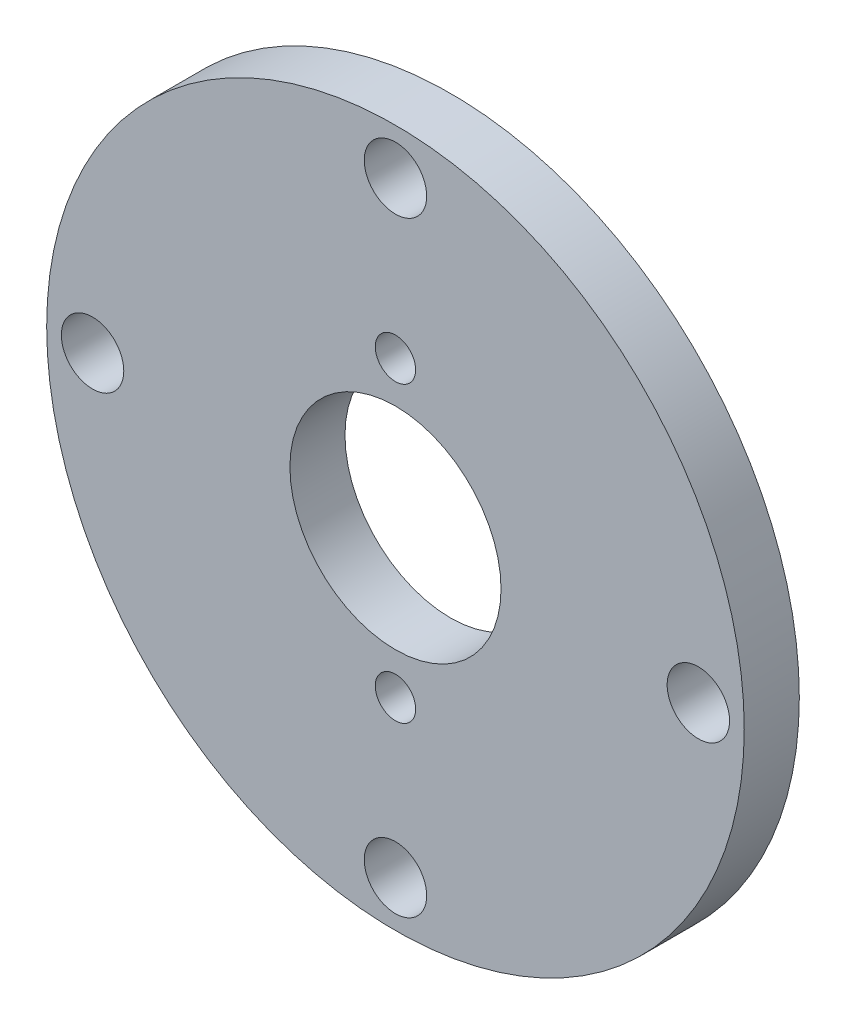
SolidWorks part; units mm, degrees
ref_plane "Front Plane" through (0, 0, 0) normal (0, 0, 1) x (1, 0, 0)
ref_plane "Top Plane" through (0, 0, 0) normal (0, 1, 0) x (1, 0, 0)
ref_plane "Right Plane" through (0, 0, 0) normal (1, 0, 0) x (0, 0, -1)
sketch "Sketch1" plane through (0, 0, 0) normal (0, 0, 1) x (1, 0, 0)
  line L0 (55, 0) -> (-55, 0) construction
  circle A0 centre (0, 8) radius 1.1
  circle A2 centre (0, -8) radius 1.1
  circle A3 centre (0, 0) radius 14
  circle A4 centre (0, 0) radius 5.75
  circle A5 centre (0, 0) radius 19
  circle A6 centre (0, 0) radius 16.5 construction
  circle A7 centre (0, 16.5) radius 1.7
  circle A8 centre (16.5, 0) radius 1.7
  circle A9 centre (0, -16.5) radius 1.7
  circle A10 centre (-16.5, 0) radius 1.7
  dimension "D1" = 2.2
  dimension "D3" = 28
  dimension "D4" = 11.5
  dimension "D5" = 38
  dimension "D7" = 3.4
  dimension "D8" = 3.4
  dimension "D9" = 3.4
  dimension "D10" = 3.4
  dimension "D2" = 8
  dimension "D6" = 2.5
extrude "Boss-Extrude1" add sketch "Sketch1" along normal blind 3 contours A5 A10 A9 A8 A7 A3 | A3 A4 A2 A0 region at (-13.604, 0, 0) region at (-18.4626, 0, 0)
